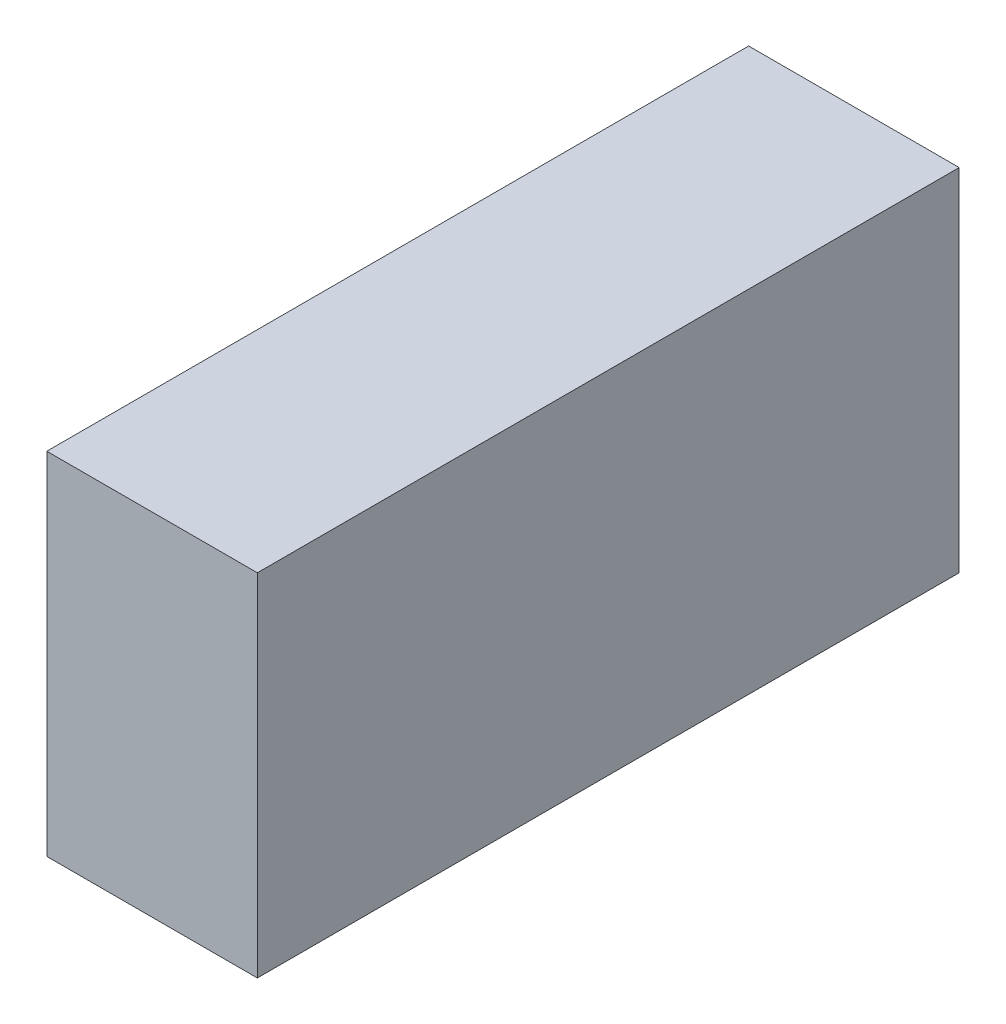
SolidWorks part; units mm, degrees
ref_plane "前视基准面" through (0, 0, 0) normal (0, 0, 1) x (1, 0, 0)
ref_plane "上视基准面" through (0, 0, 0) normal (0, 1, 0) x (1, 0, 0)
ref_plane "右视基准面" through (0, 0, 0) normal (1, 0, 0) x (0, 0, -1)
ref_plane "LEDTop" through (0, 0, 0) normal (0, 1, 0) x (1, 0, 0)
ref_plane "CenterV" through (0, 0, 0) normal (1, 0, 0) x (0, 0, -1)
ref_plane "CenterH" through (0, 0, 0) normal (0, 0, 1) x (1, 0, 0)
sketch "Circle" plane through (0, 0, 0) normal (0, 1, 0) x (1, 0, 0)
  line L0 (0, 0) -> (-200, 0) construction
  dimension "R" = 200
ref_axis "CenterAxis" through (-200, 0, 0) along (0, 1, 0)
sketch "SRectangle" plane through (0, 0, 0) normal (0, 1, 0) x (1, 0, 0)
  line L1 (-1.5, -5) -> (1.5, -5)
  line L2 (-1.5, -5) -> (-1.5, 5)
  line L3 (-1.5, 5) -> (1.5, 5)
  line L4 (1.5, -5) -> (1.5, 5)
  line L5 (-1.5, -5) -> (1.5, 5) construction
  line L6 (-1.5, 5) -> (1.5, -5) construction
  point P0 (0, 0)
  dimension "D1" = 3
  dimension "D2" = 10
extrude "FRectangle" add sketch "SRectangle" against normal blind 5
sketch "RectangleCut" plane through (0, 0, 0) normal (0, 1, 0) x (1, 0, 0)
  line L4 (-1.5, -5) -> (1.5, -5)
  line L5 (1.5, -5) -> (1.5, 5)
  line L6 (1.5, 5) -> (-1.5, 5)
  line L7 (-1.5, 5) -> (-1.5, -5)
  line L8 (-1.5, -5) -> (1.5, -5)
  line L9 (1.5, -5) -> (1.5, 5)
  line L10 (1.5, 5) -> (-1.5, 5)
  line L11 (-1.5, 5) -> (-1.5, -5)
  dimension "D1" = 0
sketch "SRound" [suppressed] plane through (0, 0, 0) normal (0, 1, 0) x (1, 0, 0)
  circle A0 centre (0, 0) radius 1
  dimension "D1" = 2
extrude "FRound" [suppressed] add sketch "SRound" against normal blind 5
sketch "RoundCut" [suppressed] plane through (0, 0, 0) normal (0, 1, 0) x (1, 0, 0)
  circle A1 centre (0, 0) radius 1
  circle A2 centre (0, 0) radius 1
  dimension "D1" = 0
equation "\"LedH\"= 5"
equation "\"D1@FRectangle\"=\"LedH\""
equation "\"D1@FRound\"=\"LedH\""
